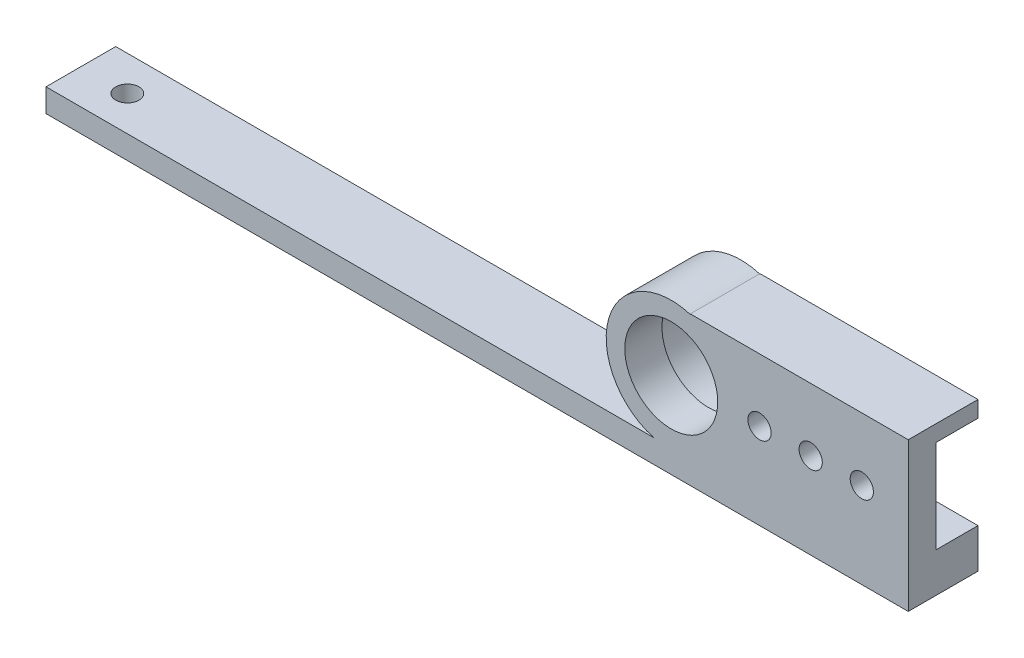
SolidWorks part; units mm, degrees
ref_plane "前视基准面" through (0, 0, 0) normal (0, 0, 1) x (1, 0, 0)
ref_plane "上视基准面" through (0, 0, 0) normal (0, 1, 0) x (1, 0, 0)
ref_plane "右视基准面" through (0, 0, 0) normal (1, 0, 0) x (0, 0, -1)
sketch "草图1" plane through (0, 0, 0) normal (0, 0, 1) x (1, 0, 0)
  line L1 (20, -10) -> (-20, -10)
  line L2 (20, -10) -> (20, 10)
  line L3 (20, 10) -> (-20, 10)
  line L4 (-20, -10) -> (-20, 10)
  line L5 (20, -10) -> (-20, 10) construction
  line L6 (20, 10) -> (-20, -10) construction
  point P0 (0, 0)
  dimension "D1" = 40
  dimension "D2" = 20
extrude "凸台-拉伸1" add sketch "草图1" along normal blind 6
sketch "草图2" plane through (0, 0, 6) normal (0, 0, 1) x (1, 0, 0)
  line L0 (20, -10) -> (20, 10) construction
  circle A0 centre (10, 0) radius 2.5
  circle A1 centre (-1, 0) radius 2.5
  circle A2 centre (-12, 0) radius 2.5
  dimension "D1" = 10
  dimension "D2" = 5
  dimension "D3" = 3
extrude "切除-拉伸1" cut sketch "草图2" against normal through all
sketch "草图3" plane through (0, 0, 6) normal (0, 0, 1) x (1, 0, 0)
  line L0 (20, 13.5) -> (20, 10)
  line L1 (20, -13.5) -> (-26.894, -13.5)
  line L3 (20, 13.5) -> (-26.894, 13.5)
  line L4 (-20, 10) -> (-20, -10)
  line L5 (-20, -10) -> (20, -10)
  line L6 (20, -10) -> (20, 10)
  line L7 (20, 10) -> (-20, 10)
  line L8 (-20, 10) -> (-20, -10)
  line L9 (-20, -10) -> (20, -10)
  line L10 (20, -10) -> (20, 10)
  line L11 (20, 10) -> (-20, 10)
  line L12 (-26.894, -13.5) -> (-26.894, 13.5)
  line L13 (20, -10.0394) -> (-26.894, 13.5) construction
  line L14 (20, 10.0394) -> (-26.894, -13.5) construction
  line L15 (20, -10) -> (20, -13.5)
  circle A0 centre (-31, 0) radius 11
  circle A1 centre (-31, 0) radius 14
  point P2 (0, 0)
  line M10 (-20, 10) -> (-20, -10)
  line M11 (-20, -10) -> (20, -10)
  line M13 (20, 10) -> (-20, 10)
  dimension "D3" = 22
  dimension "D4" = 28
  dimension "D2" = 3.5
  dimension "D1" = 0
extrude "凸台-拉伸2" add sketch "草图3" against normal blind 15 contours L3 A1 L1 L12 A0 | A1 L1 L15 M11 M10 | L1 A1 L8 A0 L12 | L8 A1 L3 L12 A0 | L8 A1 | A1 L0 L3 M10 M13 region at (-1.9449, 11.7771, 6) region at (-1.9449, -11.7771, 6) region at (-23.0173, 9.0328, 6) region at (-27.2274, 11.7946, 6) region at (-18.7882, 0, 6) region at (-23.0173, -9.0328, 6)
sketch "草图5" plane through (0, 0, 6) normal (0, 0, 1) x (1, 0, 0)
  circle A0 centre (-31, 0) radius 10
  circle A1 centre (-31, 0) radius 11 construction
  circle A2 centre (-31, 0) radius 11
  dimension "D1" = 20
extrude "凸台-拉伸3" add sketch "草图5" against normal blind 8
sketch "草图6" plane through (0, 0, 6) normal (0, 0, 1) x (1, 0, 0)
  circle A0 centre (-31, 0) radius 8.5
  circle A1 centre (-31, 0) radius 10 construction
  circle A2 centre (-31, 0) radius 10
  dimension "D1" = 17
sketch "草图8" plane through (0, 0, 6) normal (0, 0, 1) x (1, 0, 0)
  line L0 (20, -13.5) -> (20, 13.5) construction
  line L1 (20, -13.5) -> (-26.894, -13.5) construction
  line L2 (20, 13.5) -> (-26.894, 13.5) construction
  line L3 (20, -13.5) -> (20, 13.5)
  line L4 (20, -13.5) -> (-26.894, -13.5)
  line L5 (20, 13.5) -> (-26.894, 13.5)
  line L6 (-45, -14) -> (-26.894, -13.5)
  line L7 (-45, -14) -> (-239, -14)
  line L8 (-45, -14) -> (-45, 14)
  line L9 (-45, 14) -> (-239, 14)
  line L10 (-239, -14) -> (-239, 14)
  line L11 (-45, -14) -> (-239, 14) construction
  line L12 (-45, 14) -> (-239, -14) construction
  line L13 (-45, 14) -> (-26.894, 13.3843)
  line L14 (-12, 0) -> (-31, 0)
  arc A0 (-26.894, 13.3843) -> (-26.894, -13.3843) centre (-31, 0) ccw construction
  arc A1 (-26.894, 13.3843) -> (-26.894, -13.3843) centre (-31, 0) ccw
  point P6 (-142, 0)
  dimension "D1" = 28
  dimension "D2" = 194
  dimension "D3" = 14
sketch "草图9" plane through (0, -13.5, 0) normal (0, -1, 0) x (1, 0, 0)
  circle A0 centre (10.5344, 0) radius 5.2388
sketch "草图10" plane through (20, 0, 0) normal (1, 0, 0) x (0, 0, -1)
  line L1 (9, -13.5) -> (-6, -13.5)
  line L2 (9, -13.5) -> (9, -18.5)
  line L3 (9, -18.5) -> (-6, -18.5)
  line L4 (-6, -13.5) -> (-6, -18.5)
  dimension "D1" = 5
extrude "凸台-拉伸4" add sketch "草图10" against normal blind 500
sketch "草图11" plane through (0, 0, -9) normal (0, 0, -1) x (-1, 0, 0)
  line L1 (22.0371, -11.3638) -> (33.5283, -11.3638)
  line L2 (22.0371, -11.3638) -> (22.0371, -16.4864)
  line L3 (22.0371, -16.4864) -> (33.5283, -16.4864)
  line L4 (33.5283, -11.3638) -> (33.5283, -16.4864)
extrude "凸台-拉伸5" add sketch "草图11" against normal through all
sketch "草图12" plane through (0, -18.5, 0) normal (0, -1, 0) x (1, 0, 0)
  line L0 (-165.5205, -69.7347) -> (-165.5205, 6)
  line L1 (-165.5205, 109.1717) -> (-165.5205, -260.8283) construction
  line L2 (-165.5205, -69.7347) -> (-49.8553, -69.7347) construction
  line L3 (-480, 6) -> (20, 6) construction
sketch "草图13" plane through (0, -18.5, 0) normal (0, -1, 0) x (1, 0, 0)
  line L1 (-165.5205, -69.7347) -> (-490.0472, -69.7347)
  line L2 (-165.5205, -69.7347) -> (-165.5205, 14.9475)
  line L3 (-165.5205, 14.9475) -> (-490.0472, 14.9475)
  line L4 (-490.0472, -69.7347) -> (-490.0472, 14.9475)
extrude "切除-拉伸2" cut sketch "草图13" against normal through all
sketch "草图14" plane through (0, -18.5, 0) normal (0, -1, 0) x (1, 0, 0)
  line L0 (-165.5205, 6) -> (-165.5205, -9) construction
  line L1 (-165.5205, -1.5) -> (-155.5205, -1.5) construction
  circle A0 centre (-155.5205, -1.5) radius 2.5
  dimension "D1" = 5
  dimension "D2" = 10
extrude "切除-拉伸3" cut sketch "草图14" against normal blind 10
